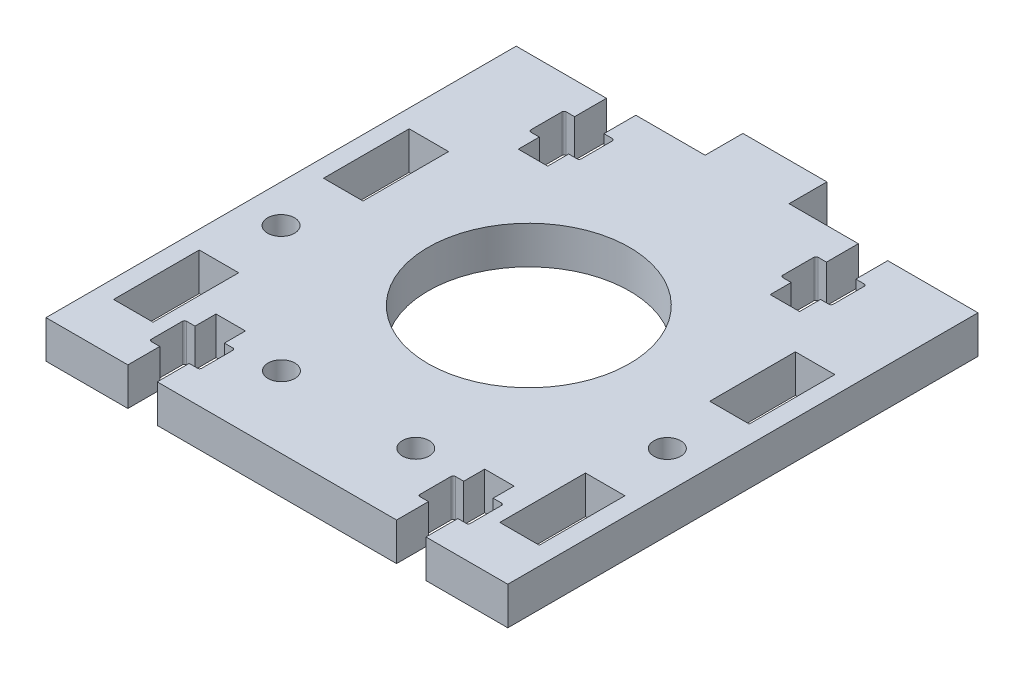
SolidWorks part; units mm, degrees
ref_plane "Front Plane" through (0, 0, 0) normal (0, 0, 1) x (1, 0, 0)
ref_plane "Top Plane" through (0, 0, 0) normal (0, 1, 0) x (1, 0, 0)
ref_plane "Right Plane" through (0, 0, 0) normal (1, 0, 0) x (0, 0, -1)
sketch "Sketch1" plane through (0, 0, 0) normal (0, 1, 0) x (1, 0, 0)
  line L1 (-27.5, 28) -> (27.5, 28)
  line L2 (-27.5, 28) -> (-27.5, -28)
  line L3 (-27.5, -28) -> (27.5, -28)
  line L4 (27.5, 28) -> (27.5, -28)
  line L5 (-27.5, 28) -> (27.5, -28) construction
  line L6 (-27.5, -28) -> (27.5, 28) construction
  point P0 (0, 0)
  dimension "D1" = 55
  dimension "D2" = 56
extrude "MainShape" add sketch "Sketch1" along normal blind 4.5
sketch "Sketch2" plane through (0, 4.5, 0) normal (0, 1, 0) x (1, 0, 0)
  line L0 (0, -28) -> (0, 28) construction
  line L1 (-27.5, -28) -> (27.5, -28) construction
  line L2 (27.5, 28) -> (-27.5, 28) construction
  line L4 (-5, 32.5) -> (5, 32.5)
  line L5 (-5, 32.5) -> (-5, 23.5)
  line L6 (-5, 23.5) -> (5, 23.5)
  line L7 (5, 32.5) -> (5, 23.5)
  line L8 (-5, 32.5) -> (5, 23.5) construction
  line L9 (-5, 23.5) -> (5, 32.5) construction
  dimension "D2" = 4.5
extrude "Tab1" add sketch "Sketch2" against normal through all
sketch "Sketch4" plane through (0, 4.5, 0) normal (0, 1, 0) x (1, 0, 0)
  line L0 (0, 32.5) -> (0, -28) construction
  line L1 (5, 32.5) -> (-5, 32.5) construction
  line L2 (-27.5, -28) -> (27.5, -28) construction
  line L3 (-15, 28) -> (-15, 17.5) construction
  line L4 (-5, 28) -> (-27.5, 28) construction
  line L5 (-13.25, 17.5) -> (-16.75, 17.5) construction
  line L6 (-16.75, 17.5) -> (-16.75, 28) construction
  line L7 (-13.25, 17.5) -> (-16.75, 17.5)
  line L8 (-16.75, 17.5) -> (-16.75, 20)
  line L9 (-16.75, 20) -> (-17.75, 20)
  line L10 (-18, 20.25) -> (-18, 23.95)
  line L11 (-17.75, 24.2) -> (-16.75, 24.2)
  line L12 (-16.75, 24.2) -> (-16.75, 28)
  line L13 (-16.75, 28) -> (-13.25, 28)
  line L14 (-13.25, 17.5) -> (-13.25, 28) construction
  line L15 (-13.25, 24.2) -> (-13.25, 28)
  line L16 (-12.25, 24.2) -> (-13.25, 24.2)
  line L17 (-12, 20.25) -> (-12, 23.95)
  line L18 (-13.25, 20) -> (-12.25, 20)
  line L19 (-13.25, 17.5) -> (-13.25, 20)
  line L20 (13.25, 17.5) -> (13.25, 28) construction
  line L21 (16.75, 17.5) -> (16.75, 28) construction
  line L22 (13.25, 17.5) -> (16.75, 17.5) construction
  line L23 (15, 28) -> (15, 17.5) construction
  line L24 (13.25, 17.5) -> (13.25, 20)
  line L25 (13.25, 20) -> (12.25, 20)
  line L26 (12, 20.25) -> (12, 23.95)
  line L27 (12.25, 24.2) -> (13.25, 24.2)
  line L28 (13.25, 24.2) -> (13.25, 28)
  line L29 (16.75, 28) -> (13.25, 28)
  line L30 (16.75, 24.2) -> (16.75, 28)
  line L31 (17.75, 24.2) -> (16.75, 24.2)
  line L32 (18, 20.25) -> (18, 23.95)
  line L33 (16.75, 20) -> (17.75, 20)
  line L34 (16.75, 17.5) -> (16.75, 20)
  line L35 (13.25, 17.5) -> (16.75, 17.5)
  arc A0 (-17.75, 20) -> (-18, 20.25) centre (-17.75, 20.25) cw
  arc A1 (-12, 20.25) -> (-12.25, 20) centre (-12.25, 20.25) cw
  arc A2 (-12.25, 24.2) -> (-12, 23.95) centre (-12.25, 23.95) cw
  arc A3 (-18, 23.95) -> (-17.75, 24.2) centre (-17.75, 23.95) cw
  arc A4 (18, 23.95) -> (17.75, 24.2) centre (17.75, 23.95) ccw
  arc A5 (12.25, 24.2) -> (12, 23.95) centre (12.25, 23.95) ccw
  arc A6 (12, 20.25) -> (12.25, 20) centre (12.25, 20.25) ccw
  arc A7 (17.75, 20) -> (18, 20.25) centre (17.75, 20.25) ccw
  point P24 (-18, 20)
  point P27 (-12, 20)
  point P30 (-12, 24.2)
  point P33 (-18, 24.2)
  point P56 (18, 24.2)
  point P57 (12, 24.2)
  point P58 (12, 20)
  point P59 (18, 20)
  dimension "D7" = 0.25
  dimension "D1" = 10.5
  dimension "D2" = 1.75
  dimension "D3" = 4.2
  dimension "D4" = 3
  dimension "D5" = 8
  dimension "D6" = 15
extrude "Cut-Extrude2" cut sketch "Sketch4" against normal through all
sketch "Sketch5" plane through (0, 4.5, 0) normal (0, 1, 0) x (1, 0, 0)
  line L0 (0, -28) -> (0, 32.5) construction
  line L1 (-27.5, -28) -> (27.5, -28) construction
  line L2 (5, 32.5) -> (-5, 32.5) construction
  line L3 (23, 28) -> (23, -28) construction
  line L4 (27.5, 28) -> (16.75, 28) construction
  line L5 (-23, 28) -> (-23, -28) construction
  line L6 (20.65, 13.1) -> (25.35, 13.1)
  line L7 (20.65, 13.1) -> (20.65, 2.9)
  line L8 (20.65, 2.9) -> (25.35, 2.9)
  line L9 (25.35, 13.1) -> (25.35, 2.9)
  line L10 (20.65, 13.1) -> (25.35, 2.9) construction
  line L11 (20.65, 2.9) -> (25.35, 13.1) construction
  line L12 (-20.65, 2.9) -> (-25.35, 13.1) construction
  line L13 (-20.65, 13.1) -> (-25.35, 2.9) construction
  line L14 (-25.35, 13.1) -> (-25.35, 2.9)
  line L15 (-20.65, 2.9) -> (-25.35, 2.9)
  line L16 (-20.65, 13.1) -> (-20.65, 2.9)
  line L17 (-20.65, 13.1) -> (-25.35, 13.1)
  line L18 (-27.5, -4.5) -> (27.5, -4.5) construction
  line L19 (-27.5, 28) -> (-27.5, -28) construction
  line L20 (27.5, -28) -> (27.5, 28) construction
  line L21 (-20.65, -22.1) -> (-25.35, -11.9) construction
  line L22 (-20.65, -11.9) -> (-25.35, -22.1) construction
  line L23 (20.65, -11.9) -> (25.35, -22.1) construction
  line L24 (20.65, -22.1) -> (25.35, -11.9) construction
  line L25 (-20.65, -22.1) -> (-25.35, -22.1)
  line L26 (-20.65, -22.1) -> (-20.65, -11.9)
  line L27 (-20.65, -11.9) -> (-25.35, -11.9)
  line L28 (-25.35, -22.1) -> (-25.35, -11.9)
  line L29 (25.35, -22.1) -> (25.35, -11.9)
  line L30 (20.65, -11.9) -> (25.35, -11.9)
  line L31 (20.65, -22.1) -> (20.65, -11.9)
  line L32 (20.65, -22.1) -> (25.35, -22.1)
  line L33 (-20.65, 13.1) -> (-25.35, 2.9) construction
  circle A0 centre (23, -4.5) radius 1.6
  circle A1 centre (-23, -4.5) radius 1.6
  point P10 (23, 8)
  point P21 (-23, 8)
  point P36 (-23, -17)
  point P37 (23, -17)
  dimension "D6" = 3.2
  dimension "D1" = 23
  dimension "D2" = 10.2
  dimension "D3" = 4.7
  dimension "D4" = 20
  dimension "D5" = 25
extrude "Cut-Extrude3" cut sketch "Sketch5" against normal through all
sketch "Sketch6" plane through (0, 4.5, 0) normal (0, 1, 0) x (1, 0, 0)
  line L0 (0, -28) -> (0, 28) construction
  line L1 (5, 32.5) -> (-5, 32.5) construction
  line L3 (-27.5, 2) -> (27.5, 2) construction
  line L4 (-27.5, 28) -> (-27.5, -28) construction
  line L5 (27.5, -28) -> (27.5, 28) construction
  line L6 (27.5, 28) -> (16.75, 28) construction
  line L7 (-27.5, -28) -> (27.5, -28) construction
  line L9 (-27.5, 28) -> (27.5, 28) construction
  circle A0 centre (0, 2) radius 12
  point P4 (0, 32.5)
  dimension "D1" = 24
  dimension "D2" = 26
extrude "Cut-Extrude4" cut sketch "Sketch6" against normal through all
sketch "Sketch7" plane through (0, 4.5, 0) normal (0, 1, 0) x (1, 0, 0)
  line L0 (0, 2) -> (0, -28) construction
  line L3 (-27.5, -28) -> (27.5, -28) construction
  line L4 (8, -19.46) -> (-8, -19.46) construction
  circle A1 centre (-8, -19.46) radius 1.6
  circle A2 centre (8, -19.46) radius 1.6
  point P8 (0, -19.46)
  dimension "D1" = 3.2
  dimension "D2" = 8
  dimension "D3" = 21.46
extrude "Cut-Extrude5" [suppressed] cut sketch "Sketch7" against normal through all
sketch "Sketch8" plane through (0, 4.5, 0) normal (0, 1, 0) x (1, 0, 0)
  line L0 (-12, 2) -> (12, 2) construction
  line L1 (0, 2) -> (0, -19.46) construction
  line L2 (8, -19.46) -> (-8, -19.46) construction
  line L3 (0, -10) -> (0, 14) construction
  circle A0 centre (-8, -19.46) radius 1.6
  circle A1 centre (0, 2) radius 12 construction
  circle A2 centre (8, -19.46) radius 1.6
  dimension "D2" = 8
  dimension "D3" = 3.2
  dimension "D1" = 90
  dimension "D4" = 21.46
extrude "Cut-Extrude6" cut sketch "Sketch8" against normal through all
sketch "Sketch9" plane through (0, 4.5, 0) normal (0, 1, 0) x (1, 0, 0)
  line L0 (0, -28) -> (0, 32.5) construction
  line L1 (-27.5, -28) -> (27.5, -28) construction
  line L2 (5, 32.5) -> (-5, 32.5) construction
  line L3 (16, -28) -> (16, -17.5) construction
  line L4 (14.25, -17.5) -> (17.75, -17.5) construction
  line L5 (17.75, -17.5) -> (17.75, -28) construction
  line L6 (17.75, -28) -> (17.75, -24.2)
  line L7 (17.75, -24.2) -> (18.75, -24.2)
  line L8 (19, -23.95) -> (19, -20.25)
  line L9 (18.75, -20) -> (17.75, -20)
  line L10 (17.75, -20) -> (17.75, -17.5)
  line L11 (17.75, -17.5) -> (14.25, -17.5)
  line L12 (17.75, -28) -> (14.25, -28)
  line L13 (14.25, -17.5) -> (14.25, -28) construction
  line L14 (14.25, -20) -> (14.25, -17.5)
  line L15 (13.25, -20) -> (14.25, -20)
  line L16 (13, -23.95) -> (13, -20.25)
  line L17 (14.25, -24.2) -> (13.25, -24.2)
  line L18 (14.25, -28) -> (14.25, -24.2)
  line L19 (-14.25, -17.5) -> (-14.25, -28) construction
  line L20 (-17.75, -17.5) -> (-17.75, -28) construction
  line L21 (-14.25, -17.5) -> (-17.75, -17.5) construction
  line L22 (-16, -28) -> (-16, -17.5) construction
  line L23 (-14.25, -28) -> (-14.25, -24.2)
  line L24 (-14.25, -24.2) -> (-13.25, -24.2)
  line L25 (-13, -23.95) -> (-13, -20.25)
  line L26 (-13.25, -20) -> (-14.25, -20)
  line L27 (-14.25, -20) -> (-14.25, -17.5)
  line L28 (-17.75, -28) -> (-14.25, -28)
  line L29 (-17.75, -17.5) -> (-14.25, -17.5)
  line L30 (-17.75, -20) -> (-17.75, -17.5)
  line L31 (-18.75, -20) -> (-17.75, -20)
  line L32 (-19, -23.95) -> (-19, -20.25)
  line L33 (-17.75, -24.2) -> (-18.75, -24.2)
  line L34 (-17.75, -28) -> (-17.75, -24.2)
  arc A0 (18.75, -24.2) -> (19, -23.95) centre (18.75, -23.95) ccw
  arc A1 (19, -20.25) -> (18.75, -20) centre (18.75, -20.25) ccw
  arc A2 (13, -20.25) -> (13.25, -20) centre (13.25, -20.25) cw
  arc A3 (13.25, -24.2) -> (13, -23.95) centre (13.25, -23.95) cw
  arc A4 (-13.25, -24.2) -> (-13, -23.95) centre (-13.25, -23.95) ccw
  arc A5 (-13, -20.25) -> (-13.25, -20) centre (-13.25, -20.25) ccw
  arc A6 (-19, -20.25) -> (-18.75, -20) centre (-18.75, -20.25) cw
  arc A7 (-18.75, -24.2) -> (-19, -23.95) centre (-18.75, -23.95) cw
  point P16 (19, -24.2)
  point P19 (19, -20)
  point P30 (13, -20)
  point P31 (13, -24.2)
  point P54 (-13, -24.2)
  point P55 (-13, -20)
  point P56 (-19, -20)
  point P57 (-19, -24.2)
  dimension "D7" = 0.25
  dimension "D1" = 10.5
  dimension "D2" = 1.75
  dimension "D3" = 8
  dimension "D4" = 4.2
  dimension "D5" = 3
  dimension "D6" = 16
extrude "Cut-Extrude7" cut sketch "Sketch9" against normal through all
sketch "Sketch10" plane through (0, 0, 28) normal (0, 0, 1) x (1, 0, 0)
  line L0 (-27.5, 2.25) -> (27.5, 2.25) construction
  line L1 (-27.5, 4.5) -> (-27.5, 0) construction
  line L2 (27.5, 4.5) -> (27.5, 0) construction
  line L3 (-16, 4.5) -> (-16, 0) construction
  line L4 (-14.25, 4.5) -> (-17.75, 4.5) construction
  line L5 (16, 4.5) -> (16, 0) construction
  line L6 (17.75, 4.5) -> (14.25, 4.5) construction
  line L7 (17.75, 0) -> (14.25, 0) construction
  line L8 (-14.25, 0) -> (-17.75, 0) construction
  circle A0 centre (-16, 2.25) radius 1.6
  circle A1 centre (16, 2.25) radius 1.6
  dimension "D1" = 3.2
  dimension "D2" = 3.2
equation "\"X-ROD-SPACING\"=45"
equation "\"Y-ROD-SPACING\"=75"
equation "\"Z-ROD-SPACING\"=17.5"
equation "\"Y-BED-OFFSET\"=2"
equation "\"Y-BED-ROD-INSET\"=3.5"
equation "\"Y-BED-SCREW-SPACING\"=209"
equation "\"Y-BED-SCREW-CUTOUT-SLOT-HEIGHT\"=1"
equation "\"T-SLOT-NUT-FILLET-RADIUS\"=0.25"
equation "\"T-SLOT-SCREW-SHAFT-RADIUS\"=1.75"
equation "\"T-SLOT-SCREW-SHAFT-CUTOUT-LENGTH\"=10.5"
equation "\"T-SLOT-NUT-DEPTH\"=4.2"
equation "\"T-SLOT-NUT-WIDTH\"=3"
equation "\"T-SLOT-NUT-END-DISTANCE\"=8"
equation "\"ACRYLIC-THICKNESS\"=10"
equation "\"ACRYLIC-THICKNESS2\"=4.5"
equation "\"ACRYLIC-TAB-CUTOUT-SIZE\"=\"ACRYLIC-THICKNESS\"+\"ACRYLIC-TAB-TOLERANCE\"*2"
equation "\"ACRYLIC-TAB-WIDTH\"=\"ACRYLIC-THICKNESS\""
equation "\"ACRYLIC-M3-HOLE\"=3.2"
equation "\"SMOOTHROD-CAP-SCREW-DISTANCE\"=20"
equation "\"FRAME-WIDTH-INNER\"=370"
equation "\"NEMA17-HOLE-SPACING\"=31"
equation "\"NEMA17-CENTRAL-CUTOUT\"=22.5"
equation "\"Z-BRACKET-REACH\"=55"
equation "\"Z-ROD-INSET\"=16"
equation "\"TOP-BRACKET-SPACING\"=40"
equation "\"SMOOTHROD-X-LENGTH\"=350"
equation "\"SMOOTHROD-Y-LENGTH\"=350"
equation "\"SMOOTHROD-Z-LENGTH\"=350"
equation "\"SMOOTHROD-TIGHTENING-HEADROOM\"=1"
equation "\"LEADSCREW-Z-LENGTH\"=300"
equation "\"SCREW-LENGTH-FRAME\"=\"ACRYLIC-THICKNESS\" + 10"
equation "\"SCREW-LENGTH-MOTOR\"=\"ACRYLIC-THICKNESS\" + 5"
equation "\"SCREW-LENGTH-EXTRUDER\"=28"
equation "\"SCREW-HEAD-RADIUS\"=6"
equation "\"PRINTED-X-SMOOTHROD-DIAMETER\"=8.2"
equation "\"PRINTED-X-SMOOTHROD-CUTOUT\"=10"
equation "\"PRINTED-X-BASE-HEIGHT\"=10"
equation "\"PRINTED-LM8UU-CUTOUT-SIZE\"=16"
equation "\"PRINTED-LM8UU-CUTOUT-LENGTH\"=24.5"
equation "\"PRINTED-X-IDLER-HEIGHT\"=16"
equation "\"PSU-MOUNTING-WIDTH\"=95"
equation "\"PSU-MOUNTING-HEIGHT\"=177"
equation "\"Y-BELT-TO-ROD-DISTANCE\"=20"
equation "\"SPOOL-HOLDER-ROD-SPACING\"=150"
equation "\"ACRYLIC-X-CARRIAGE-WIDTH\"=55"
equation "\"ACRYLIC-X-CARRIAGE-HEIGHT\"=75"
equation "\"ACRYLIC-X-CARRIAGE-SCREW-SPACING-X\"=15"
equation "\"ACRYLIC-X-CARRIAGE-SCREW-SPACING-Y\"=33"
equation "\"ACRYLIC-X-CARRIAGE-CENTER-TAB-SPACING\"=14"
equation "\"D1@Sketch1\"=\"ACRYLIC-X-CARRIAGE-WIDTH\""
equation "\"D1@MainShape\" = \"ACRYLIC-THICKNESS2\""
equation "\"D1@Sketch2\"=\"ACRYLIC-TAB-WIDTH\""
equation "\"D2@Sketch2\"=\"ACRYLIC-THICKNESS2\""
equation "\"D1@Sketch4\"=\"T-SLOT-SCREW-SHAFT-CUTOUT-LENGTH\""
equation "\"D2@Sketch4\"=\"T-SLOT-SCREW-SHAFT-RADIUS\""
equation "\"D3@Sketch4\"=\"T-SLOT-NUT-DEPTH\""
equation "\"D4@Sketch4\"=\"T-SLOT-NUT-WIDTH\""
equation "\"D5@Sketch4\"=\"T-SLOT-NUT-END-DISTANCE\""
equation "\"D6@Sketch4\"=\"ACRYLIC-X-CARRIAGE-SCREW-SPACING-X\""
equation "\"D7@Sketch4\"=\"T-SLOT-NUT-FILLET-RADIUS\""
equation "\"ACRYLIC-X-CARRIAGE-EXTRUDER-SHELF-DEPTH\"=\"ACRYLIC-X-CARRIAGE-EXTRUDER-OFFSET\" + 30"
equation "\"D2@Sketch1\"=\"ACRYLIC-X-CARRIAGE-EXTRUDER-SHELF-DEPTH\""
equation "\"ACRYLIC-X-CARRIAGE-LM8UU-CUTOUT-WIDTH\"=24.25"
equation "\"ACRYLIC-X-CARRIAGE-EXTRUDER-BRACE-SPACING\"=23"
equation "\"ACRYLIC-X-CARRIAGE-EXTRUDER-BRACE-TAB-OFFSET\"=20"
equation "\"ACRYLIC-X-CARRIAGE-EXTRUDER-BRACE-HEIGHT\"=35"
equation "\"ACRYLIC-X-CARRIAGE-EXTRUDER-BRACE-SCREW-SPACING\"=22"
equation "\"D1@Sketch5\"=\"ACRYLIC-X-CARRIAGE-EXTRUDER-BRACE-SPACING\""
equation "\"D2@Sketch5\"=\"ACRYLIC-TAB-CUTOUT-SIZE\""
equation "\"D3@Sketch5\"=\"ACRYLIC-THICKNESS2\"+\"ACRYLIC-TAB-TOLERANCE\"*2"
equation "\"D4@Sketch5\"=\"ACRYLIC-X-CARRIAGE-EXTRUDER-BRACE-TAB-OFFSET\""
equation "\"D1@Sketch7\"=\"ACRYLIC-M3-HOLE\""
equation "\"D3@Sketch8\"=\"ACRYLIC-M3-HOLE\""
equation "\"ACRYLIC-X-CARRIAGE-EXTRUDER-ANGLE\"=90"
equation "\"D1@Sketch8\"=\"ACRYLIC-X-CARRIAGE-EXTRUDER-ANGLE\""
equation "\"ACRYLIC-X-CARRIAGE-EXTRUDER-OFFSET\"=26"
equation "\"D2@Sketch6\"=\"ACRYLIC-X-CARRIAGE-EXTRUDER-OFFSET\""
equation "\"D6@Sketch5\"=\"ACRYLIC-M3-HOLE\""
equation "\"D1@Sketch9\"=\"T-SLOT-SCREW-SHAFT-CUTOUT-LENGTH\""
equation "\"D2@Sketch9\"=\"T-SLOT-SCREW-SHAFT-RADIUS\""
equation "\"D3@Sketch9\"=\"T-SLOT-NUT-END-DISTANCE\""
equation "\"D4@Sketch9\"=\"T-SLOT-NUT-DEPTH\""
equation "\"D5@Sketch9\"=\"T-SLOT-NUT-WIDTH\""
equation "\"D7@Sketch9\"=\"T-SLOT-NUT-FILLET-RADIUS\""
equation "\"ACRYLIC-TAB-TOLERANCE\"=.1"
